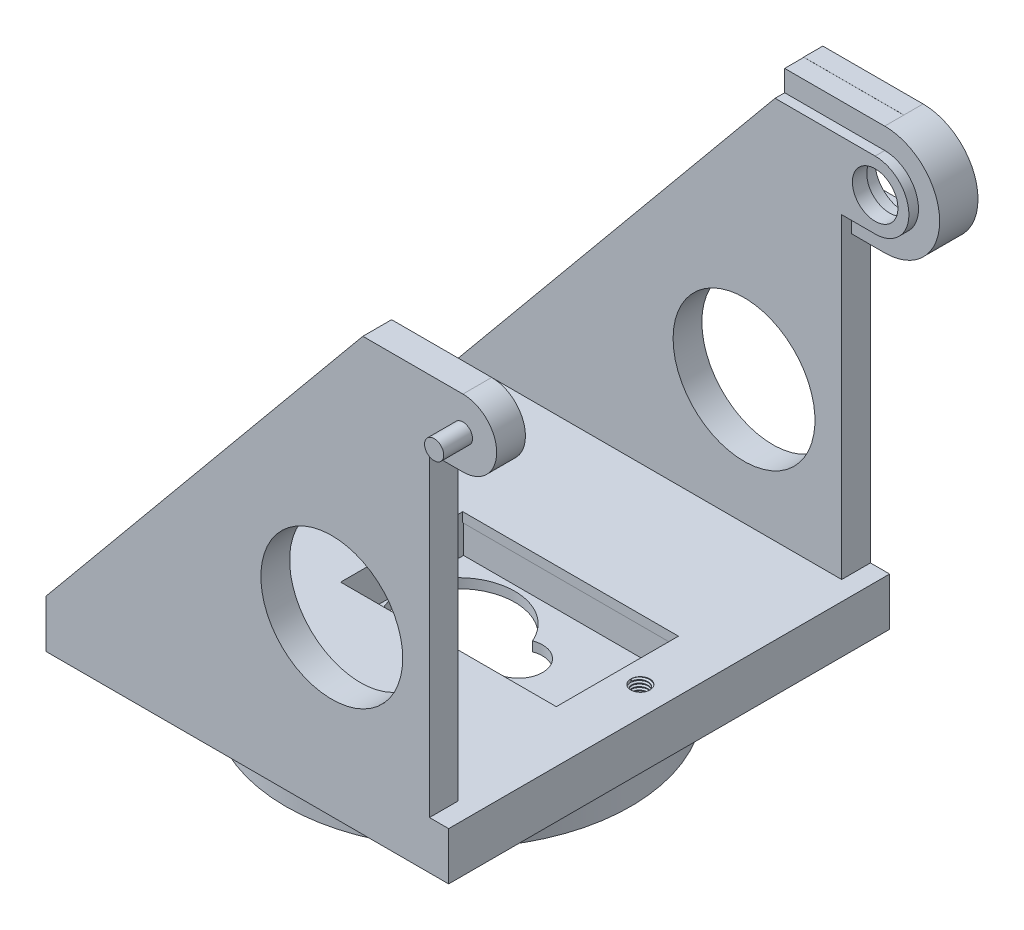
SolidWorks part; units mm, degrees
ref_plane "前视基准面" through (0, 0, 0) normal (0, 0, 1) x (1, 0, 0)
ref_plane "上视基准面" through (0, 0, 0) normal (0, 1, 0) x (1, 0, 0)
ref_plane "右视基准面" through (0, 0, 0) normal (1, 0, 0) x (0, 0, -1)
sketch "草图1" plane through (0, 0, 0) normal (0, 1, 0) x (1, 0, 0)
  line L1 (-20, 20) -> (20, 20)
  line L2 (-20, 20) -> (-20, -20)
  line L3 (-20, -20) -> (20, -20)
  line L4 (20, 20) -> (20, -20)
  line L5 (-20, 20) -> (20, -20) construction
  line L6 (-20, -20) -> (20, 20) construction
  point P0 (0, 0)
  dimension "D1" = 40
extrude "凸台-拉伸1" add sketch "草图1" along normal blind 5 contours L2 L1 L4 L3
sketch "草图2" plane through (0, 0, 0) normal (0, -1, 0) x (1, 0, 0)
  circle A0 centre (0, 0) radius 18
  arc A2 (-0.4429, -0.5857) -> (0.4429, 0.5857) centre (0, 0) ccw construction
sketch "草图5" plane through (0, 5, 0) normal (0, 1, 0) x (1, 0, 0)
  line L0 (0, 0) -> (-10.9705, 0) construction
  line L1 (-10.6, -0.6106) -> (-10.6, -5.9) construction
  line L2 (10.6, -6.3693) -> (-10.6, -6.3693)
  line L3 (10.6, -6.3693) -> (10.6, 6.3693)
  line L4 (10.6, 6.3693) -> (-10.6, 6.3693)
  line L5 (-10.6, -6.3693) -> (-10.6, 6.3693)
  line L6 (10.6, -6.3693) -> (-10.6, 6.3693) construction
  line L7 (10.6, 6.3693) -> (-10.6, -6.3693) construction
  point P1 (0, 0)
extrude "切除-拉伸6" cut sketch "草图5" against normal blind 1
sketch "草图7" plane through (0, 4, 0) normal (0, 1, 0) x (1, 0, 0)
  line L0 (-10.6, -6.3693) -> (10.6, -6.3693) construction
  line L1 (16.6, 6.4559) -> (-5.9, 6.4559)
  line L2 (16.6, 6.4559) -> (16.6, -6.3693)
  line L3 (16.6, -6.3693) -> (-5.9, -6.3693)
  line L4 (-5.9, 6.4559) -> (-5.9, -6.3693)
  line L5 (16.6, 5.9) -> (16.6, -5.9) construction
  line L12 (-5.9, 0) -> (-5.9, 5.9) construction
  point P0 (0, 0)
extrude "切除-拉伸9" cut sketch "草图7" against normal blind 3
sketch "草图8" plane through (0, 1, 0) normal (0, 1, 0) x (1, 0, 0)
  arc A0 (5.4167, 2.3387) -> (5.4167, -2.3387) centre (0, 0) ccw
  arc A1 (5.4167, -2.3387) -> (5.4167, 2.3387) centre (6.3, 0) ccw
  arc A6 (5.3442, 2.5) -> (5.3442, -2.5) centre (0, 0) ccw construction
  arc A7 (8.8, 0) -> (6.3, 2.5) centre (6.3, 0) ccw construction
  arc A8 (6.3, -2.5) -> (8.8, 0) centre (6.3, 0) ccw construction
extrude "切除-拉伸10" cut sketch "草图8" against normal blind 3 contours A0 A1
sketch "草图9" plane through (0, 0, 20) normal (0, 0, 1) x (1, 0, 0)
  line L0 (20, 45) -> (23.489, 45)
  line L1 (-20, 5) -> (13.0495, 45)
  line L3 (20, 5) -> (20, 37.9589)
  line L4 (-20, 0) -> (20, 0)
  line L5 (20, 0) -> (20, 5)
  line L6 (20, 5) -> (-20, 5)
  line L7 (-20, 5) -> (-20, 0)
  line L8 (-20, 0) -> (20, 0)
  line L9 (20, 0) -> (20, 5)
  line L11 (-20, 5) -> (-20, 0)
  line L12 (20, 45) -> (13.0495, 45)
  line L13 (-20, 0) -> (20, 0)
  line L14 (-20, 5) -> (-20, 0)
  line L15 (20, 5) -> (-20, 5)
  line L16 (20, 0) -> (20, 5)
  line L17 (-20, 0) -> (20, 0)
  line L18 (-20, 5) -> (-20, 0)
  line L20 (20, 0) -> (20, 5)
  line L24 (23.489, 37.9589) -> (20, 37.9589)
  arc A2 (23.489, 37.9589) -> (23.489, 45) centre (23.489, 41.4794) ccw
  point P14 (23.489, 41.4794)
  dimension "D1" = 0
  dimension "D2" = 0
extrude "凸台-拉伸4" add sketch "草图9" along normal blind 3 contours L8 L9 L3 L24 A2 L0 L12 L1 L11
sketch "草图10" plane through (0, 0, 23) normal (0, 0, 1) x (1, 0, 0)
  line L6 (-20, 5) -> (-20, 0)
  line L7 (-20, 0) -> (20, 0)
  line L8 (20, 0) -> (20, 37.9589)
  line L9 (20, 37.9589) -> (23.489, 37.9589)
  line L10 (23.489, 45) -> (13.0495, 45)
  line L11 (13.0495, 45) -> (-20, 5)
  line L12 (-20, 5) -> (-20, 0)
  line L13 (-20, 0) -> (20, 0)
  line L14 (20, 0) -> (20, 37.9589)
  line L15 (20, 37.9589) -> (23.489, 37.9589)
  line L16 (23.489, 45) -> (13.0495, 45)
  circle A0 centre (23.489, 41.4794) radius 1
  arc A1 (23.489, 37.9589) -> (23.489, 45) centre (23.489, 41.4794) ccw
  arc A2 (23.489, 37.9589) -> (23.489, 45) centre (23.489, 41.4794) ccw
  dimension "D1" = 0
extrude "凸台-拉伸5" add sketch "草图10" along normal blind 3 contours A0
sketch "草图11" plane through (0, 0, 23) normal (0, 0, 1) x (1, 0, 0)
  circle A0 centre (9.8114, 17.9827) radius 7.399
extrude "切除-拉伸11" cut sketch "草图11" against normal blind 3
sketch "草图12" plane through (0, 0, -20) normal (0, 0, -1) x (-1, 0, 0)
  line L0 (-20, 0) -> (-20, 37.9589)
  line L1 (-20, 37.9589) -> (-23.489, 37.9589)
  line L3 (-23.489, 45) -> (-13.0495, 45)
  line L4 (-13.0495, 45) -> (20, 5)
  line L5 (20, 5) -> (20, 0)
  line L6 (20, 0) -> (-20, 0)
  arc A0 (-23.489, 45) -> (-23.489, 37.9589) centre (-23.489, 41.4794) ccw
extrude "凸台-拉伸6" add sketch "草图12" along normal blind 3
sketch "草图13" plane through (0, 0, -23) normal (0, 0, -1) x (-1, 0, 0)
  line L0 (-14.3521, 44.4794) -> (-12.6194, 44.4794)
  line L2 (-20, 37.9589) -> (-10.4267, 37.9589)
  line L3 (-23.489, 44.4794) -> (-14.3521, 44.4794)
  line L4 (-10.4267, 38.4794) -> (-10.4267, 37.9589)
  line L5 (-11.9502, 38.4794) -> (-23.489, 38.4794)
  line L6 (-11.9502, 38.4794) -> (-10.4267, 38.4794)
  line L8 (20, 5) -> (-13.0495, 45) construction
  line L9 (-20, 37.9589) -> (-23.489, 37.9589)
  line L10 (-12.6194, 44.4794) -> (-13.0495, 45)
  line L11 (-13.0495, 45) -> (-23.489, 45)
  line L15 (-20, 0) -> (20, 0)
  line L16 (20, 0) -> (20, 5)
  line L17 (20, 5) -> (-13.0495, 45)
  line L18 (-13.0495, 45) -> (-23.489, 45)
  line L19 (-23.489, 37.9589) -> (-20, 37.9589)
  line L20 (-20, 37.9589) -> (-20, 0)
  line L21 (-20, 0) -> (20, 0)
  line L22 (20, 0) -> (20, 5)
  line L23 (20, 5) -> (-12.6194, 44.4794)
  line L26 (-20, 37.9589) -> (-20, 0)
  arc A0 (-23.489, 44.4794) -> (-23.489, 38.4794) centre (-23.489, 41.4794) ccw
  arc A1 (-23.489, 45) -> (-23.489, 37.9589) centre (-23.489, 41.4794) ccw
  arc A2 (-23.489, 45) -> (-23.489, 37.9589) centre (-23.489, 41.4794) ccw
  dimension "D1" = 0
  dimension "D2" = 6
sketch "草图15" plane through (0, 0, -23) normal (0, 0, -1) x (-1, 0, 0)
  circle A0 centre (-23.489, 41.4794) radius 2.3755
extrude "切除-拉伸12" cut sketch "草图15" against normal blind 3
sketch "草图16" plane through (0, 0, -23) normal (0, 0, -1) x (-1, 0, 0)
  circle A0 centre (-9.8114, 17.9827) radius 7.399
  circle A1 centre (-9.8114, 17.9827) radius 7.399 construction
extrude "切除-拉伸13" cut sketch "草图16" against normal blind 3
sketch "草图18" plane through (0, 5, 0) normal (0, 1, 0) x (1, 0, 0)
  line L0 (10.6, 6.3693) -> (20, 6.3693)
  line L1 (20, 20) -> (20, -20) construction
  line L2 (10.6, -6.3693) -> (20, -6.3693)
  line L3 (20, -6.3693) -> (20, 6.3693)
  line L4 (10.6, -6.3693) -> (10.6, 6.3693)
extrude "切除-拉伸14" cut sketch "草图18" against normal blind 1
ref_plane "基准面1" through (0.4429, 2, 0.5857) normal (0.7976, 0, -0.6031) x (-0.6031, 0, -0.7976)
sketch "草图20" plane through (0, 4, 0) normal (0, 1, 0) x (1, 0, 0)
  line L3 (-5.9, 6.3693) -> (-10.6, 6.3693)
  line L4 (-5.9, -6.3693) -> (-5.9, 6.3693)
  line L7 (-10.6, -6.3693) -> (-5.9, -6.3693)
  line L8 (-10.6, 6.3693) -> (20, 6.3693)
  line L9 (20, 6.3693) -> (20, 20)
  line L10 (20, 20) -> (-20, 20)
  line L11 (-20, 20) -> (-20, -20)
  line L12 (-20, -20) -> (20, -20)
  line L13 (20, -20) -> (20, -6.3693)
  line L14 (20, -6.3693) -> (-10.6, -6.3693)
  line L15 (-5.9, 6.3693) -> (-10.6, 6.3693)
  line L16 (-10.6, 6.3693) -> (20, 6.3693)
  line L17 (20, 6.3693) -> (20, 20)
  line L18 (20, 20) -> (-20, 20)
  line L19 (-20, 20) -> (-20, -20)
  line L20 (-20, -20) -> (20, -20)
  line L21 (20, -20) -> (20, -6.3693)
  line L22 (20, -6.3693) -> (-10.6, -6.3693)
  line L24 (-5.9, -6.3693) -> (-5.9, 6.3693)
  line L27 (-10.6, -6.3693) -> (-5.9, -6.3693)
  line L28 (-10.6, 6.3693) -> (-10.6, -6.3693)
  line L29 (-10.6, 6.3693) -> (-10.6, -6.3693)
  line L31 (-10.6, -6.3693) -> (-10.6, 6.3693)
  line L32 (-10.6, -6.3693) -> (-10.6, 6.3693)
  dimension "D1" = 0
  dimension "D2" = 0
extrude "凸台-拉伸9" add sketch "草图20" against normal blind 1 contours L29 L27 L24 L15
sketch "草图22" plane through (0, 4, 0) normal (0, 1, 0) x (1, 0, 0)
  line L0 (-5.9, 6.3693) -> (-10.6, 6.3693)
  line L1 (-10.6, 6.3693) -> (-10.6, -6.3693)
  line L2 (-10.6, -6.3693) -> (-5.9, -6.3693)
  line L3 (-5.9, -6.3693) -> (-5.9, 6.3693)
extrude "凸台-拉伸10" add sketch "草图22" along normal blind 1
sketch "草图23" plane through (0, 4, 0) normal (0, 1, 0) x (1, 0, 0)
  line L0 (16.6, 6.3693) -> (16.6, -6.3693)
  line L1 (16.6, -6.3693) -> (20, -6.3693)
  line L2 (20, -6.3693) -> (20, 6.3693)
  line L3 (20, 6.3693) -> (16.6, 6.3693)
extrude "凸台-拉伸11" add sketch "草图23" along normal blind 1
sketch "草图24" plane through (0, 5, 0) normal (0, 1, 0) x (1, 0, 0)
  circle A0 centre (-8.279, 0.0197) radius 1
  arc A1 (-7.279, 0.0197) -> (-9.0553, 0.65) centre (-8.279, 0.0197) ccw construction
extrude "切除-拉伸16" cut sketch "草图24" against normal blind 2
thread "螺纹线1" pitch 0.3175 method extrude profile "螺纹线轮廓1" start angle 0, offset 0, length 2, pitch 0.3175, diameter 2
ref_plane "基准面2" through (-9.279, 5, -0.0197) normal (0, 0, 1) x (-1, 0, 0)
sketch "螺纹线轮廓1" plane through (-9.279, 5, -0.0197) normal (0, 0, 1) x (-1, 0, 0)
  line L0 (0, 0) -> (0, 0.3175) construction
  line L11 (0, 0) -> (0, 0.2778)
  line L12 (0, 0.2778) -> (-0.1719, 0.1786)
  line L13 (-0.1719, 0.1786) -> (-0.1719, 0.0992)
  line L15 (-0.1719, 0.0992) -> (0, 0)
  line L17 (-0.1719, 0.1389) -> (0, 0.1389) construction
  point P2 (0, 0)
  dimension "Pitch" = 0.3175
  dimension "Profile_Angle" = 60
  dimension "Profile_Land" = 0.0794
  dimension "Profile_Height" = 0.1719
sketch "草图28" plane through (0, 5, 0) normal (0, 1, 0) x (1, 0, 0)
  circle A0 centre (18.979, 0.0197) radius 1
  arc A1 (19.7553, 0.65) -> (19.7553, -0.6106) centre (18.979, 0.0197) ccw construction
extrude "切除-拉伸17" cut sketch "草图28" against normal blind 2
thread "螺纹线2" pitch 0.3175 method extrude profile "螺纹线轮廓2" start angle 0, offset 0, length 2, pitch 0.3175, diameter 2
ref_plane "基准面3" through (17.979, 5, -0.0197) normal (0, 0, 1) x (-1, 0, 0)
sketch "螺纹线轮廓2" plane through (17.979, 5, -0.0197) normal (0, 0, 1) x (-1, 0, 0)
  line L0 (0, 0) -> (0, 0.3175) construction
  line L11 (0, 0) -> (0, 0.2778)
  line L12 (0, 0.2778) -> (-0.1719, 0.1786)
  line L13 (-0.1719, 0.1786) -> (-0.1719, 0.0992)
  line L15 (-0.1719, 0.0992) -> (0, 0)
  line L17 (-0.1719, 0.1389) -> (0, 0.1389) construction
  point P2 (0, 0)
  dimension "Pitch" = 0.3175
  dimension "Profile_Angle" = 60
  dimension "Profile_Land" = 0.0794
  dimension "Profile_Height" = 0.1719
ref_plane "基准面4" through (-24.273, -10.5, 19.0544) normal (-0.9992, 0, -0.0396) x (-0.0396, 0, 0.9992)
ref_plane "基准面5" through (26.8453, -10.5, 17.0757) normal (-0.0396, 0, 0.9992) x (0.9992, 0, 0.0396)
sketch "草图36" plane through (0, 0, 0) normal (0, -1, 0) x (1, 0, 0)
  circle A0 centre (0, 0) radius 16.5
  circle A1 centre (0, 0) radius 18 construction
extrude "凸台-拉伸13" add sketch "草图2" along normal blind 6.5 contours A0
extrude "切除-拉伸19" cut sketch "草图36" along normal blind 8 contours A0
sketch "草图39" plane through (0, 0, -23) normal (0, 0, -1) x (-1, 0, 0)
  line L1 (-13.0495, 45) -> (-12.6194, 44.4794)
  line L10 (-23.8406, 37.3546) -> (-13.0295, 37.3546)
  line L11 (-13.0295, 35.751) -> (-13.0295, 37.3546)
  line L12 (-23.489, 35.751) -> (-13.0295, 35.751)
  line L14 (-23.489, 47.2079) -> (-13.0295, 47.2079)
  line L18 (-23.8406, 45.6043) -> (-13.0295, 45.6043)
  line L20 (-13.0295, 47.2079) -> (-13.0295, 45.6043)
  arc A0 (-23.8406, 45.6043) -> (-23.8406, 37.3546) centre (-23.489, 41.4794) ccw
  arc A1 (-23.489, 47.2079) -> (-23.489, 35.751) centre (-23.489, 41.4794) ccw
  line M9 (-20, 37.9589) -> (-20, 0)
extrude "凸台-拉伸14" add sketch "草图39" along normal blind 2 contours L14 A1 L12 L10 A0 L18 L20 M9 | L12 L11 L10 M9 region at (21.9203, 37.1562, -23) region at (16.5147, 36.5528, -23)
sketch "草图41" plane through (0, 0, -23) normal (0, 0, -1) x (-1, 0, 0)
  circle A0 centre (-12.0097, 41.2557) radius 0.4383
extrude "切除-拉伸20" cut sketch "草图41" against normal blind 2.5
sketch "草图44" plane through (0, 0, -23) normal (0, 0, 1) x (1, 0, 0)
  line L0 (23.489, 45) -> (23.489, 47.2079)
  line L1 (23.489, 37.9589) -> (23.489, 35.751)
  arc A0 (23.489, 37.9589) -> (23.489, 45) centre (23.489, 41.4794) ccw
  arc A1 (23.489, 35.751) -> (23.489, 47.2079) centre (23.489, 41.4794) ccw
extrude "凸台-拉伸21" add sketch "草图44" along normal blind 2
sketch "草图46" plane through (0, 0, -23) normal (0, 0, 1) x (1, 0, 0)
  line L0 (20, 35.751) -> (20, 37.9589)
  line L1 (20, 37.9589) -> (23.489, 37.9589)
  line L2 (23.489, 37.9589) -> (23.489, 35.751)
  line L7 (23.489, 35.751) -> (23.489, 37.3546)
  line L8 (23.489, 37.3546) -> (20, 37.3546)
  line L9 (20, 37.3546) -> (20, 35.751)
  line L10 (20, 35.751) -> (23.489, 35.751)
  line L14 (20, 35.751) -> (23.489, 35.751)
  dimension "D1" = 0
extrude "凸台-拉伸22" add sketch "草图46" along normal blind 2
sketch "草图48" plane through (0, 45, 0) normal (0, 1, 0) x (1, 0, 0)
  line L0 (13.0495, 23) -> (23.489, 23)
  line L1 (23.489, 23) -> (23.489, 21)
  line L2 (23.489, 21) -> (13.0495, 21)
  line L3 (13.0495, 23) -> (13.0495, 20) construction
  line L9 (13.0495, 20) -> (23.489, 20)
  line L10 (23.489, 20) -> (23.489, 21)
  line L11 (23.489, 21) -> (23.489, 23)
  line L12 (23.489, 23) -> (13.0495, 23)
  line L13 (13.0495, 23) -> (13.0495, 20)
  line L18 (13.0495, 23) -> (13.0495, 21)
  dimension "D1" = 0
extrude "凸台-拉伸23" add sketch "草图48" along normal blind 2.2
ref_plane "基准面7" through (19.4629, 36.2352, -13.65) normal (0, 0, 1) x (1, 0, 0)
ref_plane "基准面9" through (11.658, 41.5852, -24.5411) normal (-0.9999, 0.0089, -0.009) x (-0.009, -0.0002, 1)
sketch "草图59" plane through (0, 0, -23) normal (0, 0, -1) x (-1, 0, 0)
  circle A0 centre (-23.489, 41.4794) radius 3.0207
  circle A1 centre (-23.489, 41.4794) radius 2.3755
  circle A2 centre (-23.489, 41.4794) radius 3.0207 construction
extrude "切除-拉伸27" cut sketch "草图59" against normal blind 1.5
sketch "草图62" plane through (20, 0, 0) normal (1, 0, 0) x (0, 0, -1)
  line L0 (-20, 5) -> (-23, 5)
  line L1 (-23, 0) -> (-23, 37.9589) construction
  line L2 (-23, 5) -> (-23, 0)
  line L3 (-23, 0) -> (23, 0)
  line L4 (23, 0) -> (23, 5)
  line L5 (23, 5) -> (20, 5)
  line L6 (20, 5) -> (-20, 5)
extrude "凸台-拉伸25" add sketch "草图62" along normal blind 2
